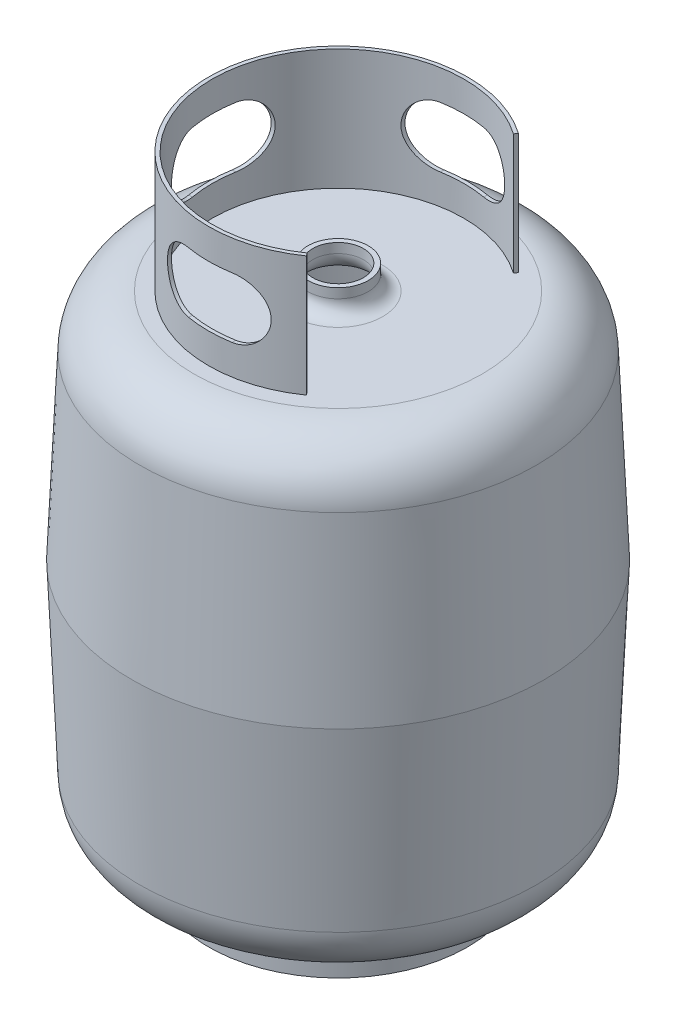
SolidWorks part; units mm, degrees
material "1060 Alloy"
ref_plane "Front Plane" through (0, 0, 0) normal (0, 0, 1) x (1, 0, 0)
ref_plane "Top Plane" through (0, 0, 0) normal (0, 1, 0) x (1, 0, 0)
ref_plane "Right Plane" through (0, 0, 0) normal (1, 0, 0) x (0, 0, -1)
sketch "Sketch1" plane through (0, 0, 0) normal (0, 0, 1) x (1, 0, 0)
  line L0 (0, -262.6647) -> (0, 262.6647) construction
  line L1 (-457.4052, 0) -> (457.4052, 0) construction
  line L2 (0, 213.75) -> (-25, 213.75)
  line L3 (-25, 213.75) -> (-25, 205.75)
  line L4 (-37, 193.75) -> (-119.4219, 193.75)
  line L5 (-164.379, 150.7129) -> (-170.9593, 0)
  line L6 (-170.9593, 0) -> (-164.379, -150.7129)
  line L7 (-119.4219, -193.75) -> (0, -193.75)
  line L8 (0, -193.75) -> (0, 213.75)
  arc A0 (-119.4219, -193.75) -> (-164.379, -150.7129) centre (-119.4219, -148.75) cw
  arc A1 (-164.379, 150.7129) -> (-119.4219, 193.75) centre (-119.4219, 148.75) cw
  arc A2 (-37, 193.75) -> (-25, 205.75) centre (-37, 205.75) ccw
  point P4 (0, 0)
  point P7 (0, 0)
  point P16 (-162.5, -193.75)
  point P19 (-162.5, 193.75)
  point P22 (-25, 193.75)
  dimension "D8" = 45
  dimension "D9" = 12
  dimension "D1" = 387.5
  dimension "D2" = 162.5
  dimension "D3" = 162.5
  dimension "D4" = 25
  dimension "D5" = 20
  dimension "D6" = 92.5
  dimension "D7" = 92.5
revolve "Revolve1" add sketch "Sketch1" angle 360 about L8
shell "Shell2" thickness 4 removed face at (25, 213.75, 0)
sketch "Sketch3" plane through (0, 193.75, 0) normal (0, 1, 0) x (1, 0, 0)
  line L0 (0, 0) -> (208.7099, 0) construction
  line L1 (0, 0) -> (61.6147, 87.9948)
  line L2 (0, 0) -> (61.6147, -87.9948)
  arc A0 (61.6147, 87.9948) -> (61.6147, -87.9948) centre (0, 0) ccw
  arc A1 (59.8939, 85.5374) -> (59.8939, -85.5374) centre (0, 0) ccw
  circle A2 centre (0, 0) radius 119.4219 construction
  dimension "D1" = 12
  dimension "D2" = 3
  dimension "D3" = 55
  dimension "D4" = 55
extrude "Boss-Extrude2" add sketch "Sketch3" along normal blind 100 contours A1 L1 A0 L2 region at (-107.1556, 193.75, 0)
sketch "Sketch4" plane through (0, 0, 0) normal (0, 0, 1) x (1, 0, 0)
  line L0 (0, 0) -> (0, 423.2895) construction
  line L1 (-18, 243.75) -> (18, 243.75) construction
  line L2 (-18, 268.75) -> (18, 268.75)
  line L3 (-18, 218.75) -> (18, 218.75)
  line L4 (59.8939, 293.75) -> (-104.4219, 293.75) construction
  arc A0 (-18, 268.75) -> (-18, 218.75) centre (-18, 243.75) ccw
  arc A1 (18, 218.75) -> (18, 268.75) centre (18, 243.75) ccw
  point P5 (0, 243.75)
  dimension "D1" = 18
  dimension "D2" = 36
  dimension "D3" = 50
  dimension "D4" = 50
extrude "Cut-Extrude1" cut sketch "Sketch4" against normal mid plane 478
pattern_circular "CirPattern1" count 2 every 90 about axis through (0, 293.75, 0) along (0, 1, 0) of "Cut-Extrude1"
sketch "Sketch5" plane through (0, -193.75, 0) normal (0, -1, 0) x (1, 0, 0)
  circle A0 centre (0, 0) radius 107.4219
  circle A1 centre (0, 0) radius 104.4219
  circle A2 centre (0, 0) radius 119.4219 construction
  dimension "D1" = 12
  dimension "D2" = 3
extrude "Boss-Extrude3" add sketch "Sketch5" along normal blind 30
